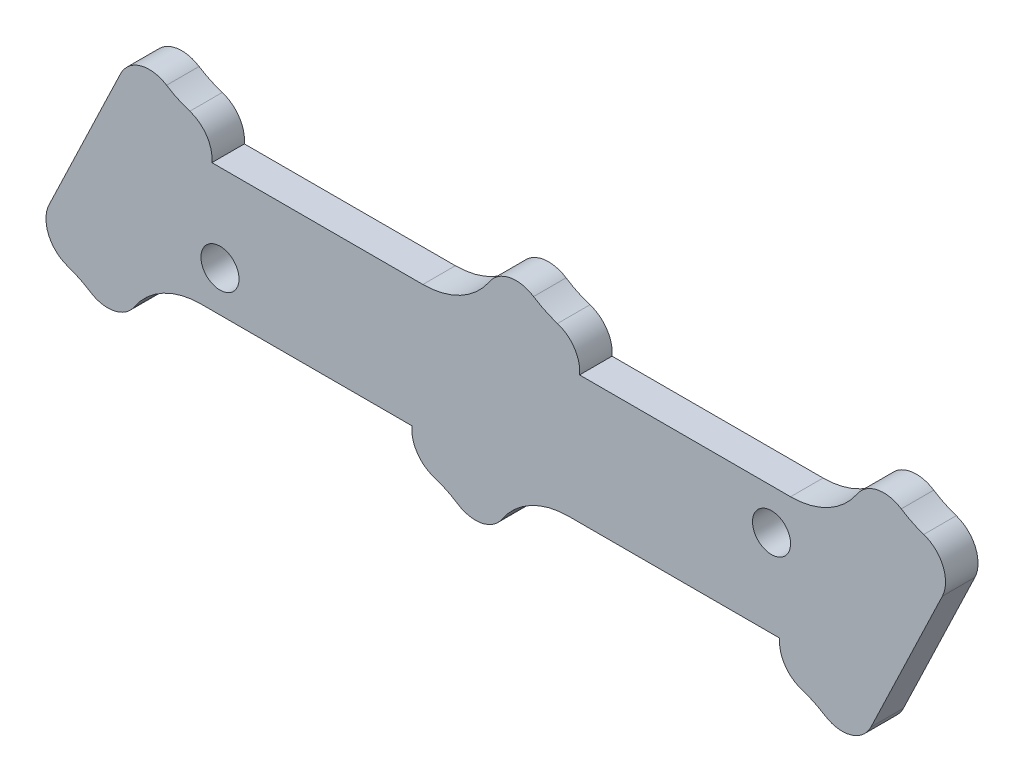
SolidWorks part; units mm, degrees
material "3003-H14"
ref_plane "X-Y Datum" through (0, 0, 0) normal (0, 0, 1) x (1, 0, 0)
ref_plane "X-Z Datum" through (0, 0, 0) normal (0, 1, 0) x (1, 0, 0)
ref_plane "Y-Z Datum" through (0, 0, 0) normal (1, 0, 0) x (0, 0, -1)
sketch "Sketch3" plane through (0, 0, 0) normal (0, 0, 1) x (1, 0, 0)
  line L0 (10.775, 10.775) -> (22.275, 34.775) construction
  line L1 (0, 0) -> (156.4633, 0) construction
  line L2 (0, 0) -> (0, 56.3098) construction
  line L3 (0, 56.3098) -> (156.4633, 56.3098) construction
  line L4 (156.4633, 0) -> (156.4633, 56.3098) construction
  line L5 (33.775, 10.775) -> (45.275, 34.775) construction
  line L6 (56.775, 10.775) -> (68.275, 34.775) construction
  line L7 (16.525, 22.775) -> (62.525, 22.775) construction
  line L8 (33.775, 10.775) -> (22.275, 34.775) construction
  line L9 (45.275, 34.775) -> (56.775, 10.775) construction
  line L10 (10.775, 10.775) -> (33.775, 10.775) construction
  line L11 (56.775, 10.775) -> (33.775, 10.775) construction
  line L12 (22.275, 34.775) -> (45.275, 34.775) construction
  line L13 (68.275, 34.775) -> (45.275, 34.775) construction
  line L14 (22.275, 34.775) -> (22.275, 10.775) construction
  line L15 (45.275, 10.775) -> (45.275, 34.775) construction
  line L16 (33.775, 10.775) -> (33.775, 34.775) construction
  line L17 (56.775, 34.775) -> (56.775, 10.775) construction
  line L18 (13.4804, 9.4786) -> (24.9804, 33.4786)
  line L19 (36.4804, 9.4786) -> (47.9804, 33.4786)
  line L20 (59.4804, 9.4786) -> (70.9804, 33.4786)
  line L21 (8.0696, 12.0714) -> (19.5696, 36.0714)
  line L22 (31.0696, 12.0714) -> (42.5696, 36.0714)
  line L23 (54.0696, 12.0714) -> (65.5696, 36.0714)
  line L24 (17.935, 18.775) -> (57.2817, 18.775)
  line L25 (21.7683, 26.775) -> (61.115, 26.775)
  line L26 (16.525, 26.775) -> (62.525, 26.775) construction
  line L27 (16.525, 18.775) -> (62.525, 18.775) construction
  line L48 (56.775, 10.775) -> (68.275, 10.775) construction
  line L49 (68.275, 10.775) -> (68.275, 34.775) construction
  circle A0 centre (10.775, 10.775) radius 10.775 construction
  circle A1 centre (33.775, 10.775) radius 10.775 construction
  circle A2 centre (22.275, 34.775) radius 10.775 construction
  circle A3 centre (45.275, 34.775) radius 10.775 construction
  circle A4 centre (68.275, 34.775) radius 10.775 construction
  circle A5 centre (56.775, 10.775) radius 10.775 construction
  circle A6 centre (10.775, 10.775) radius 4.7 construction
  circle A7 centre (33.775, 10.775) radius 4.7 construction
  circle A8 centre (56.775, 10.775) radius 4.7 construction
  circle A9 centre (68.275, 34.775) radius 4.7 construction
  circle A10 centre (45.275, 34.775) radius 4.7 construction
  circle A11 centre (22.275, 34.775) radius 4.7 construction
  circle A12 centre (22.275, 34.775) radius 6.2
  circle A13 centre (10.775, 10.775) radius 6.2
  circle A14 centre (33.775, 10.775) radius 6.2
  circle A15 centre (45.275, 34.775) radius 6.2
  circle A16 centre (68.275, 34.775) radius 6.2
  circle A17 centre (56.775, 10.775) radius 6.2
  circle A18 centre (125.775, 10.775) radius 10.775 construction
  circle A19 centre (102.775, 10.775) radius 10.775 construction
  circle A20 centre (79.775, 10.775) radius 10.775 construction
  circle A21 centre (91.275, 34.775) radius 10.775 construction
  circle A22 centre (114.275, 34.775) radius 10.775 construction
  circle A23 centre (137.275, 34.775) radius 10.775 construction
  dimension "D1" = 21.55
  dimension "D9" = 9.4
  dimension "D2" = 23
  dimension "D3" = 24
  dimension "D4" = 11.5
  dimension "D6" = 23
  dimension "D8" = 23
  dimension "D10" = 3
  dimension "D11" = 3
  dimension "D12" = 4
  dimension "D13" = 4
  dimension "D14" = 1.5
  dimension "D5" = 6
  dimension "D7" = 5
extrude "Boss-Extrude1" add sketch "Sketch3" along normal blind 2.032 contours L17 | L17 | L17 | L17 | L49 | A13 L18 A12 L21 | L25 L18 L24 L22 | L25 L22 L24 L19 | L25 L19 L24 L23 | A17 L20 A16 L23 | A14 L19 L24 L22 | A15 L22 L25 L19 region at (16.525, 22.775, 0) region at (28.025, 22.775, 0) region at (37.4676, 17.343, 0) region at (39.525, 22.775, 0) region at (41.5824, 28.207, 0) region at (51.025, 22.775, 0) region at (62.525, 22.775, 0)
ref_plane "Plane1" through (68.275, 0, 0) normal (1, 0, 0) x (0, 0, -1)
fillet "Fillet1" radius 5 4 edges at (61.115, 26.775, 1.016) (38.115, 26.775, 1.016) (40.935, 18.775, 1.016) (17.935, 18.775, 1.016)
fillet "Fillet4" radius 2 12 edges at (61.8251, 14.3718, 1.016) (56.4142, 16.9645, 1.016) (68.6358, 28.5855, 1.016) (63.2249, 31.1782, 1.016) (45.6358, 28.5855, 1.016) (40.2249, 31.1782, 1.016) (33.4142, 16.9645, 1.016) (38.8251, 14.3718, 1.016) (15.8251, 14.3718, 1.016) (10.4142, 16.9645, 1.016) (22.6358, 28.5855, 1.016) (17.2249, 31.1782, 1.016)
sketch "Sketch5" plane through (0, 0, 2.032) normal (0, 0, 1) x (1, 0, 0)
  line L0 (65.2304, 21.315) -> (12.4988, 21.315) construction
  line L2 (11.5865, 19.4111) -> (16.0526, 28.7317) construction
  line L3 (13.898, 24.235) -> (66.4728, 24.235) construction
  line L4 (44.7683, 26.775) -> (57.9665, 26.775) construction
  line L5 (21.0835, 18.775) -> (34.2817, 18.775) construction
  line L6 (56.775, 10.775) -> (68.275, 34.775) construction
  line L7 (68.275, 34.775) -> (45.275, 34.775) construction
  line L8 (45.275, 34.775) -> (56.775, 10.775) construction
  line L9 (56.775, 34.775) -> (56.775, 10.775) construction
  line L10 (33.775, 10.775) -> (22.275, 34.775) construction
  line L11 (22.275, 34.775) -> (10.775, 10.775) construction
  line L12 (10.775, 10.775) -> (33.775, 10.775) construction
  line L13 (22.275, 10.775) -> (22.275, 34.775) construction
  circle A0 centre (33.775, 24.235) radius 1.1906
  circle A1 centre (22.275, 21.315) radius 1.1906
  circle A2 centre (56.775, 24.235) radius 1.1906
  circle A3 centre (45.275, 21.315) radius 1.1906
  point P19 (56.775, 24.235)
  point P21 (22.275, 21.315)
  point P34 (45.275, 21.315)
  point P35 (33.775, 24.235)
  point P36 (33.775, 24.235)
  point P37 (0, 0)
  point P38 (13.8196, 24.0714)
  dimension "D1" = 2.3813
  dimension "D2" = 2.54
  dimension "D3" = 2.54
extrude "Cut-Extrude1" cut sketch "Sketch5" against normal through all contours A1 | A2 region at (22.275, 21.315, 2.032) region at (56.775, 24.235, 2.032)
